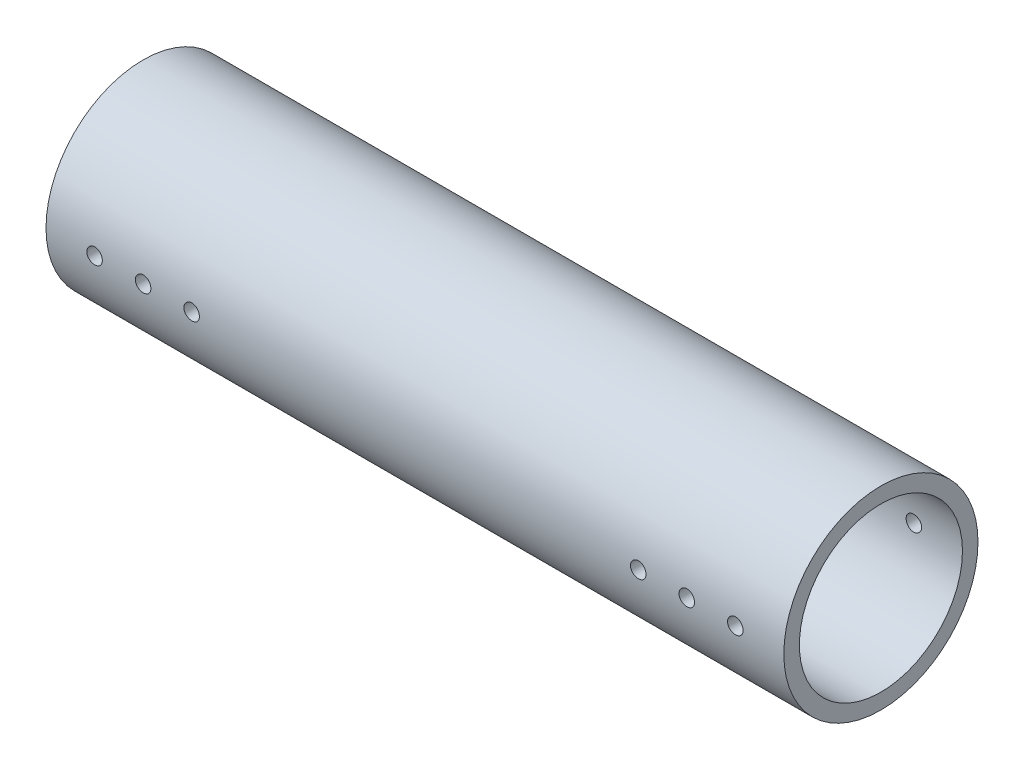
SolidWorks part; units mm, degrees
material "Zoltek Panex 33"
ref_plane "Спереди" through (0, 0, 0) normal (0, 0, 1) x (1, 0, 0)
ref_plane "Сверху" through (0, 0, 0) normal (0, 1, 0) x (1, 0, 0)
ref_plane "Справа" through (0, 0, 0) normal (1, 0, 0) x (0, 0, -1)
other "Configuration Table"
sketch "Эскиз2" plane through (0, 0, 0) normal (1, 0, 0) x (0, 0, -1)
  circle A0 centre (0, 0) radius 25
  circle A1 centre (0, 0) radius 21
  dimension "D1" = 50
  dimension "D2" = 42
extrude "Бобышка-Вытянуть2" add sketch "Эскиз2" along normal blind 190
ref_plane "Плоскость1" through (0, 0, 25) normal (0, 0, 1) x (1, 0, 0)
sketch "Эскиз4" plane through (0, 0, 25) normal (0, 0, 1) x (1, 0, 0)
  line L0 (0, -25) -> (190, -25) construction
  line L1 (190, -25) -> (190, 25) construction
  circle A0 centre (12.5, 0) radius 2
  circle A1 centre (177.5, 0) radius 2
  circle A2 centre (25, 0) radius 2
  circle A3 centre (37.5, 0) radius 2
  circle A4 centre (165, 0) radius 2
  circle A5 centre (152.5, 0) radius 2
  dimension "D1" = 4
  dimension "D4" = 4
  dimension "D6" = 4
  dimension "D8" = 4
  dimension "D10" = 4
  dimension "D11" = 4
  dimension "D2" = 12.5
  dimension "D3" = 25
  dimension "D5" = 12.5
  dimension "D7" = 12.5
  dimension "D9" = 12.5
  dimension "15" = 12.5
  dimension "D12" = 12.5
extrude "Вырез-Вытянуть2" cut sketch "Эскиз4" against normal through all and the other way blind 10 contours A0 | A1 | A2 | A3 | A5 | A4
equation "\"Diameter\"= 50мм"
equation "\"D1@Эскиз2\"= \"Diameter\""
equation "\"Length\" = 190мм"
equation "\"Thickness\"= 4мм"
equation "\"D1@Бобышка-Вытянуть2\"= \"Length\""
equation "\"D2@Эскиз2\" = \"Diameter\" - \"Thickness\" * 2"
equation "\"D4@Эскиз4\"=\"D1@Эскиз4\""
equation "\"D5@Эскиз4\"=\"D2@Эскиз4\""
equation "\"D3@Эскиз4\"=\"Diameter\"/2"
equation "\"D6@Эскиз4\"=\"D1@Эскиз4\""
equation "\"D8@Эскиз4\"=\"D6@Эскиз4\""
equation "\"D10@Эскиз4\"=\"D4@Эскиз4\""
equation "\"D11@Эскиз4\"=\"D4@Эскиз4\""
equation "\"D9@Эскиз4\"=\"D7@Эскиз4\""
